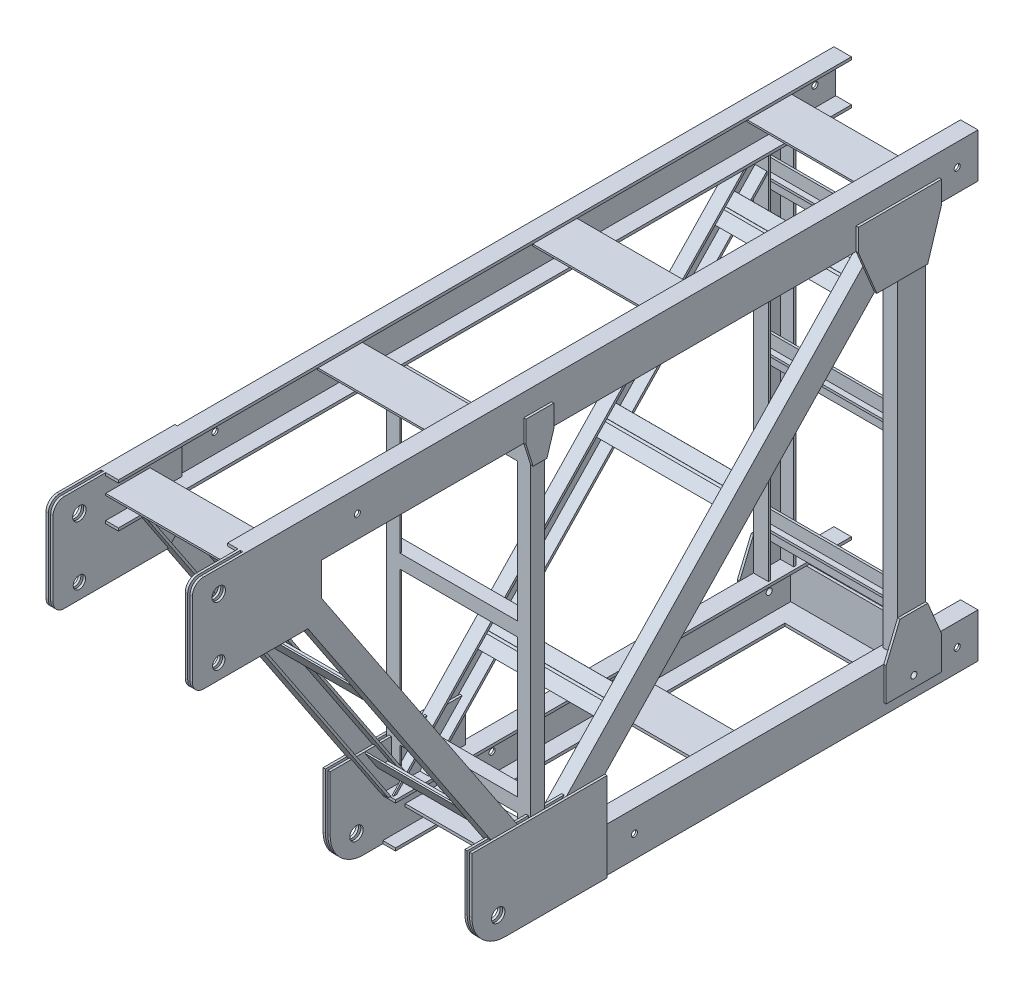
SolidWorks part; units mm, degrees
note: The reader was unsure of these and kept them because the rebuilt part matched: shared geometry of "草图38<2>".
ref_plane "前视基准面" through (0, 0, 0) normal (0, 0, 1) x (1, 0, 0)
ref_plane "上视基准面" through (0, 0, 0) normal (0, 1, 0) x (1, 0, 0)
ref_plane "右视基准面" through (0, 0, 0) normal (1, 0, 0) x (0, 0, -1)
sketch "草图2" plane through (0, 0, 0) normal (0, 0, 1) x (1, 0, 0)
  line L0 (0, 0) -> (0, 160)
  line L1 (0, 160) -> (63, 160)
  line L2 (63, 160) -> (63, 150)
  line L3 (63, 150) -> (6.5, 150)
  line L4 (6.5, 150) -> (6.5, 10)
  line L5 (6.5, 10) -> (63, 10)
  line L6 (63, 10) -> (63, 0)
  line L7 (63, 0) -> (0, 0)
  line L8 (457, 160) -> (520, 160)
  line L9 (520, 160) -> (520, 0)
  line L10 (520, 0) -> (457, 0)
  line L11 (457, 0) -> (457, 10)
  line L12 (457, 10) -> (513.5, 10)
  line L13 (513.5, 10) -> (513.5, 150)
  line L14 (513.5, 150) -> (457, 150)
  line L15 (457, 150) -> (457, 160)
  dimension "D1" = 160
  dimension "D2" = 10
  dimension "D3" = 6.5
  dimension "D4" = 63
  dimension "D5" = 520
extrude "拉伸1" add sketch "草图2" along normal blind 2835
pattern_linear "阵列(线性)2" count 2 spacing 1500 along (0, -1, 0) of "拉伸1"
sketch "草图4" plane through (0, -1340, 0) normal (0, 1, 0) x (1, 0, 0)
  line L0 (0, -2835) -> (0, 0) construction
  line L1 (520, -2835) -> (0, -2835)
  line L2 (520, -2835) -> (520, -1835)
  line L3 (520, -1835) -> (0, -1835)
  line L4 (0, -2835) -> (0, -1835)
  dimension "D1" = 1000
extrude "拉伸2" cut sketch "草图4" against normal blind 1000
sketch "草图5" plane through (0, 0, 0) normal (-1, 0, 0) x (0, 0, 1)
  line L0 (160, 95) -> (320, 95)
  line L1 (320, 95) -> (320, 88.5)
  line L2 (243.25, 88.5) -> (320, 88.5)
  line L3 (243.25, 88.5) -> (243.25, 48.5)
  line L4 (243.25, 48.5) -> (236.75, 48.5)
  line L5 (236.75, 48.5) -> (236.75, 88.5)
  line L6 (236.75, 88.5) -> (160, 88.5)
  line L7 (160, 88.5) -> (160, 95)
  line L8 (0, 160) -> (0, 0) construction
  point P10 (0, 80)
  dimension "D1" = 160
  dimension "D2" = 6.5
  dimension "D3" = 6.5
  dimension "D4" = 40
  dimension "D5" = 160
  dimension "D6" = 15
extrude "拉伸3" add sketch "草图5" against normal blind 520
sketch "草图8" plane through (0, 0, 0) normal (-1, 0, 0) x (0, 0, 1)
  line L0 (240, -1420) -> (240, 160) construction
  line L1 (2835, 160) -> (0, 160) construction
  line L2 (2835, 0) -> (0, 0) construction
  line L3 (190, 0) -> (290, 0)
  line L4 (190, 0) -> (190, -1340)
  line L5 (190, -1340) -> (290, -1340)
  line L6 (290, 0) -> (290, -1340)
  line L7 (1835, -1340) -> (0, -1340) construction
  line L9 (0, -1420) -> (1835, -1420) construction
  line L10 (0, -1340) -> (0, -1500) construction
  line L11 (1835, -1500) -> (1835, -1340) construction
  dimension "D1" = 50
  dimension "D2" = 50
  dimension "D3" = 240
extrude "拉伸7" add sketch "草图8" against normal blind 520 separate body
sketch "草图10" plane through (0, -1340, 0) normal (0, -1, 0) x (1, 0, 0)
  line L0 (466.7, 290) -> (466.7, 281.5)
  line L1 (520, 290) -> (0, 290) construction
  line L2 (466.7, 281.5) -> (514.7, 281.5)
  line L3 (514.7, 281.5) -> (514.7, 198.5)
  line L4 (514.7, 198.5) -> (466.7, 198.5)
  line L5 (466.7, 198.5) -> (466.7, 190)
  line L6 (520, 190) -> (0, 190) construction
  line L7 (53.3, 190) -> (53.3, 198.5)
  line L8 (53.3, 198.5) -> (5.3, 198.5)
  line L9 (5.3, 198.5) -> (5.3, 281.5)
  line L10 (53.3, 281.5) -> (53.3, 290)
  line L11 (53.3, 290) -> (466.7, 290)
  line L12 (5.3, 281.5) -> (53.3, 281.5)
  line L13 (53.3, 190) -> (466.7, 190)
  line L16 (0, 1835) -> (0, 0) construction
  line L17 (520, 1835) -> (520, 0) construction
  dimension "D1" = 5.3
  dimension "D2" = 5.3
  dimension "D3" = 8.5
  dimension "D4" = 48
extrude "拉伸9" cut sketch "草图10" against normal blind 1340
sketch "草图11" plane through (0, 0, 0) normal (-1, 0, 0) x (0, 0, 1)
  line L0 (2835, 160) -> (2835, 0) construction
  line L1 (2835, 80) -> (0, 80) construction
  line L2 (0, 160) -> (0, 0) construction
  circle A0 centre (2740, 80) radius 11
  dimension "D1" = 22
  dimension "D2" = 95
extrude "拉伸10" cut sketch "草图11" against normal through all
sketch "草图12" plane through (0, 0, 0) normal (-1, 0, 0) x (0, 0, 1)
  line L0 (1645, -1420) -> (290, 0) construction
  line L1 (290, 0) -> (359.1113, 0)
  line L2 (2835, 0) -> (0, 0) construction
  line L3 (359.1113, 0) -> (1637.7732, -1340)
  line L4 (1637.7732, -1340) -> (1499.5507, -1340)
  line L5 (1499.5507, -1340) -> (290, -72.4266)
  line L6 (290, -1340) -> (290, 0) construction
  line L7 (290, -72.4266) -> (290, 0)
  line L8 (0, -1420) -> (1835, -1420) construction
  line L9 (1835, -1340) -> (0, -1340) construction
  line L10 (0, -1500) -> (0, -1340) construction
  line L11 (1835, -1500) -> (1835, -1340) construction
  dimension "D1" = 50
  dimension "D2" = 50
  dimension "D3" = 190
extrude "拉伸11" add sketch "草图12" against normal blind 48
pattern_linear "阵列(线性)3" count 2 spacing 472 along (1, 0, 0) of "拉伸11"
sketch "草图13" plane through (48, 0, 0) normal (1, 0, 0) x (0, 0, -1)
  line L0 (-347.3623, 0) -> (-290, 0)
  line L1 (-359.1113, 0) -> (-290, 0) construction
  line L2 (-290, 0) -> (-290, -60.114)
  line L3 (-290, 0) -> (-290, -72.4266) construction
  line L4 (-290, -60.114) -> (-1511.2996, -1340)
  line L5 (-1499.5507, -1340) -> (-1637.7732, -1340) construction
  line L6 (-1511.2996, -1340) -> (-1626.0243, -1340)
  line L7 (-1626.0243, -1340) -> (-347.3623, 0)
  line L8 (-1637.7732, -1340) -> (-359.1113, 0) construction
  line L9 (-290, -72.4266) -> (-1499.5507, -1340) construction
  dimension "D1" = 8.5
  dimension "D2" = 8.5
extrude "拉伸12" cut sketch "草图13" against normal blind 42.7
sketch "草图14" plane through (472, 0, 0) normal (-1, 0, 0) x (0, 0, 1)
  line L0 (290, -84.7391) -> (290, 0)
  line L1 (290, 0) -> (290, -72.4266) construction
  line L2 (290, 0) -> (347.3623, 0)
  line L3 (359.1113, 0) -> (290, 0) construction
  line L4 (347.3623, 0) -> (1626.0243, -1340)
  line L5 (1499.5507, -1340) -> (1637.7732, -1340) construction
  line L6 (1626.0243, -1340) -> (1487.8018, -1340)
  line L7 (1487.8018, -1340) -> (290, -84.7391)
  line L8 (1637.7732, -1340) -> (359.1113, 0) construction
  line L9 (290, -72.4266) -> (1499.5507, -1340) construction
  dimension "D1" = 8.5
  dimension "D2" = 8.5
extrude "拉伸13" cut sketch "草图14" against normal blind 42.7
sketch "草图15" plane through (0, 0, 0) normal (-1, 0, 0) x (0, 0, 1)
  line L0 (2550, 80) -> (1550, -1420) construction
  line L1 (2496.6667, 0) -> (2448.5926, 0)
  line L2 (2835, 0) -> (359.1113, 0) construction
  line L3 (2448.5926, 0) -> (1589.197, -1289.0935)
  line L4 (1637.7732, -1340) -> (359.1113, 0) construction
  line L5 (1589.197, -1289.0935) -> (1637.7732, -1340)
  line L6 (1637.7732, -1340) -> (1651.4074, -1340)
  line L7 (1835, -1340) -> (1637.7732, -1340) construction
  line L8 (1651.4074, -1340) -> (2544.7407, 0)
  line L9 (2544.7407, 0) -> (2496.6667, 0)
  line L10 (0, -1420) -> (1835, -1420) construction
  line L11 (2740, 80) -> (0, 80) construction
  line L12 (0, 160) -> (0, 0) construction
  line L13 (1835, -1500) -> (1835, -1340) construction
  line L14 (0, -1340) -> (0, -1500) construction
  dimension "D1" = 40
  dimension "D2" = 40
  dimension "D3" = 285
  dimension "D4" = 190
extrude "拉伸14" add sketch "草图15" against normal blind 43
pattern_linear "阵列(线性)4" count 2 spacing 477 along (1, 0, 0) of "拉伸14"
sketch "草图16" plane through (477, 0, 0) normal (-1, 0, 0) x (0, 0, 1)
  line L0 (2458.2075, 0) -> (2535.1259, 0)
  line L1 (2544.7407, 0) -> (2448.5926, 0) construction
  line L2 (2535.1259, 0) -> (1641.7925, -1340)
  line L3 (1637.7732, -1340) -> (1651.4074, -1340) construction
  line L4 (1641.7925, -1340) -> (1564.8741, -1340)
  line L5 (1564.8741, -1340) -> (2458.2075, 0)
  line L6 (1651.4074, -1340) -> (2544.7407, 0) construction
  line L7 (2448.5926, 0) -> (1589.197, -1289.0935) construction
  dimension "D1" = 8
  dimension "D2" = 8
extrude "拉伸15" cut sketch "草图16" against normal blind 38
sketch "草图17" plane through (43, 0, 0) normal (1, 0, 0) x (0, 0, -1)
  line L0 (-2535.1259, 0) -> (-2458.2075, 0)
  line L1 (-2544.7407, 0) -> (-2448.5926, 0) construction
  line L2 (-2458.2075, 0) -> (-1564.8741, -1340)
  line L3 (-1637.7732, -1340) -> (-1651.4074, -1340) construction
  line L4 (-1564.8741, -1340) -> (-1641.7925, -1340)
  line L5 (-1641.7925, -1340) -> (-2535.1259, 0)
  line L6 (-1651.4074, -1340) -> (-2544.7407, 0) construction
  line L7 (-2448.5926, 0) -> (-1589.197, -1289.0935) construction
  dimension "D1" = 8
  dimension "D2" = 8
extrude "拉伸16" cut sketch "草图17" against normal blind 38
sketch "草图18" plane through (0, 0, 0) normal (-1, 0, 0) x (0, 0, 1)
  line L0 (1589.197, -1289.0935) -> (1589.197, 0.0067) construction
  line L1 (1589.197, -1289.0935) -> (359.1113, 0) construction
  line L2 (2448.5926, 0) -> (359.1113, 0) construction
  line L4 (1564.197, 0) -> (1614.197, 0)
  line L5 (1564.197, 0) -> (1564.197, -1262.8943)
  line L7 (1614.197, 0) -> (1614.197, -1251.5935)
  line L8 (2448.5926, 0) -> (1589.197, -1289.0935) construction
  line L9 (1614.197, -1251.5935) -> (1589.197, -1289.0935)
  line L10 (1589.197, -1289.0935) -> (1564.197, -1262.8943)
  dimension "D1" = 25
  dimension "D2" = 25
extrude "拉伸17" add sketch "草图18" against normal blind 520 separate body
sketch "草图19" plane through (0, 0, 0) normal (0, 1, 0) x (1, 0, 0)
  line L0 (457, -2835) -> (457, 0) construction
  line L1 (457, -1564.197) -> (63, -1564.197)
  line L2 (457, -1564.197) -> (457, -1614.197)
  line L3 (457, -1614.197) -> (63, -1614.197)
  line L4 (63, -1564.197) -> (63, -1614.197)
  line L5 (520, -1564.197) -> (0, -1564.197) construction
  line L6 (520, -1614.197) -> (0, -1614.197) construction
  line L7 (63, -2835) -> (63, 0) construction
extrude "拉伸18" cut sketch "草图19" against normal through all
sketch "草图20" plane through (457, 0, 0) normal (-1, 0, 0) x (0, 0, 1)
  line L0 (1564.197, 0) -> (1614.197, 0)
  line L1 (1614.197, 0) -> (1614.197, -1251.5935)
  line L2 (1614.197, -1251.5935) -> (1589.197, -1289.0935)
  line L3 (1589.197, -1289.0935) -> (1564.197, -1262.8943)
  line L4 (1564.197, -1262.8943) -> (1589.197, -1289.0935) construction
  line L5 (1564.197, -1262.8943) -> (1564.197, 0) construction
  line L6 (1564.197, -1262.8943) -> (1564.197, 0)
extrude "拉伸19" cut sketch "草图20" against normal blind 15
sketch "草图21" plane through (63, 0, 0) normal (1, 0, 0) x (0, 0, -1)
  line L0 (-1614.197, -1251.5935) -> (-1589.197, -1289.0935)
  line L1 (-1589.197, -1289.0935) -> (-1564.197, -1262.8943)
  line L2 (-1564.197, -1262.8943) -> (-1564.197, 0)
  line L3 (-2835, 0) -> (0, 0) construction
  line L4 (-1564.197, -1262.8943) -> (-1564.197, 0) construction
  line L5 (-1564.197, 0) -> (-1614.197, 0)
  line L6 (-1564.197, 0) -> (-1614.197, 0) construction
  line L7 (-1614.197, 0) -> (-1614.197, -1251.5935)
extrude "拉伸20" cut sketch "草图21" against normal blind 15
sketch "草图23" plane through (472, 0, 0) normal (-1, 0, 0) x (0, 0, 1)
  line L0 (1609.197, -1259.0935) -> (1589.197, -1289.0935)
  line L1 (1589.197, -1289.0935) -> (1614.197, -1251.5935) construction
  line L2 (1589.197, -1289.0935) -> (1564.197, -1262.8943)
  line L3 (1564.197, -1262.8943) -> (1564.197, 0)
  line L4 (1614.197, 0) -> (1564.197, 0) construction
  line L5 (1564.197, 0) -> (1609.197, 0)
  line L6 (1609.197, 0) -> (1609.197, -1259.0935)
  line L8 (1614.197, -1251.5935) -> (1614.197, 0) construction
  dimension "D1" = 5
extrude "拉伸21" cut sketch "草图23" against normal blind 45
sketch "草图24" plane through (48, 0, 0) normal (1, 0, 0) x (0, 0, -1)
  line L0 (-1609.197, -1259.0935) -> (-1589.197, -1289.0935)
  line L1 (-1614.197, -1251.5935) -> (-1589.197, -1289.0935) construction
  line L2 (-1589.197, -1289.0935) -> (-1564.197, -1262.8943)
  line L3 (-1564.197, -1262.8943) -> (-1564.197, 0)
  line L4 (-1564.197, 0) -> (-1609.197, 0)
  line L5 (-1564.197, 0) -> (-1614.197, 0) construction
  line L6 (-1609.197, 0) -> (-1609.197, -1259.0935)
  line L7 (-1614.197, 0) -> (-1614.197, -1251.5935) construction
  dimension "D1" = 5
extrude "拉伸22" cut sketch "草图24" against normal blind 45
pattern_linear "阵列(线性)6" count 4 spacing 775 along (0, 0, 1) of "拉伸3"
sketch "草图27" plane through (0, -1500, 0) normal (0, -1, 0) x (1, 0, 0)
  line L0 (0, 1835) -> (0, 0) construction
  line L1 (0, 240) -> (520, 240)
  line L2 (0, 240) -> (0, 80)
  line L3 (0, 80) -> (520, 80)
  line L4 (520, 240) -> (520, 80)
  line L5 (520, 1835) -> (520, 0) construction
  line L6 (0, 0) -> (63, 0) construction
  line L12 (0, 160) -> (520, 160) construction
  dimension "D1" = 160
  dimension "D2" = 80
extrude "拉伸24" add sketch "草图27" against normal blind 10
sketch "草图28" plane through (0, -1490, 0) normal (0, 1, 0) x (1, 0, 0)
  line L0 (513.5, -1835) -> (513.5, 0) construction
  line L1 (513.5, -162.5) -> (6.5, -162.5)
  line L2 (513.5, -162.5) -> (513.5, -152.5)
  line L3 (513.5, -152.5) -> (6.5, -152.5)
  line L4 (6.5, -162.5) -> (6.5, -152.5)
  line L5 (6.5, -1835) -> (6.5, 0) construction
  line L6 (63, -240) -> (63, -80) construction
  line L7 (457, -240) -> (457, -80) construction
  line L8 (63, -80) -> (457, -80) construction
  line L9 (457, -160) -> (63, -160) construction
  dimension "D1" = 10
  dimension "D2" = 5
extrude "拉伸25" add sketch "草图28" along normal blind 140
sketch "草图29" plane through (0, 0, 0) normal (-1, 0, 0) x (0, 0, 1)
  line L0 (240, -1340) -> (190, -1340) construction
  line L1 (240, -1340) -> (240, 160) construction
  line L2 (2835, 160) -> (0, 160) construction
  line L3 (231.5, -1160) -> (231.5, -1260)
  line L4 (231.5, -1260) -> (240, -1260)
  line L5 (240, -1260) -> (240, -1214.25)
  line L6 (240, -1214.25) -> (260, -1214.25)
  line L7 (260, -1214.25) -> (260, -1205.75)
  line L8 (260, -1205.75) -> (240, -1205.75)
  line L9 (240, -1205.75) -> (240, -1160)
  line L10 (240, -1160) -> (231.5, -1160)
  line L11 (190, 0) -> (190, -1340) construction
  line L12 (240, -1340) -> (290, -1340) construction
  dimension "D1" = 100
  dimension "D2" = 8.5
  dimension "D3" = 8.5
  dimension "D4" = 20
  dimension "D5" = 80
extrude "拉伸26" add sketch "草图29" against normal blind 520
pattern_linear "阵列(线性)9" count 3 spacing 550 along (0, 1, 0) of "拉伸26"
sketch "草图30" plane through (0, 0, 0) normal (-1, 0, 0) x (0, 0, 1)
  line L0 (1721.338, -1500) -> (137.3239, 160) construction
  line L1 (1835, -1500) -> (0, -1500) construction
  line L2 (2835, 160) -> (0, 160) construction
  line L3 (290, -72.4266) -> (1499.5507, -1340) construction
  line L5 (290, -72.4266) -> (326.1736, -37.9088) construction
  line L6 (326.1736, -37.9088) -> (362.3471, -3.3911) construction
  line L7 (1589.197, -1289.0935) -> (359.1113, 0) construction
  line L8 (372.0166, -98.2634) -> (441.052, -170.6106)
  line L9 (441.052, -170.6106) -> (447.2015, -164.7425)
  line L10 (447.2015, -164.7425) -> (415.6178, -131.6437)
  line L11 (415.6178, -131.6437) -> (430.0872, -117.8366)
  line L12 (430.0872, -117.8366) -> (424.2192, -111.6871)
  line L13 (424.2192, -111.6871) -> (409.7498, -125.4942)
  line L14 (409.7498, -125.4942) -> (378.1661, -92.3954)
  line L15 (378.1661, -92.3954) -> (372.0166, -98.2634)
  dimension "D1" = 100
  dimension "D2" = 8.5
  dimension "D3" = 8.5
  dimension "D4" = 20
  dimension "D5" = 80
extrude "拉伸27" add sketch "草图30" against normal blind 520
pattern_linear "阵列(线性)10" count 3 spacing 620 along (0, -0.7235, 0.6904) of "拉伸27"
sketch "草图31" plane through (520, 0, 0) normal (1, 0, 0) x (0, 0, -1)
  line L0 (-2453.9085, -59.6303) -> (-2409.5325, -126.1943)
  line L1 (-2453.9085, -59.6303) -> (-2458.0688, -62.4038)
  line L2 (-2409.5325, -126.1943) -> (-2413.6928, -128.9678)
  line L3 (-2458.0688, -62.4038) -> (-2413.6928, -128.9678)
  line L4 (-1651.4074, -1340) -> (-1618.1253, -1317.812) construction
  line L5 (-1618.1253, -1317.812) -> (-1584.8433, -1295.624) construction
  line L6 (-2603.3333, 160) -> (-1618.1253, -1317.812) construction
  line L7 (-2835, 160) -> (0, 160) construction
  line L8 (-1651.4074, -1340) -> (-2544.7407, 0) construction
  line L10 (-2448.5926, 0) -> (-1589.197, -1289.0935) construction
  line L11 (-2458.0688, -62.4038) -> (-2433.8006, -94.299) construction
  line L12 (-2453.9085, -59.6303) -> (-2413.6928, -128.9678) construction
  line L13 (-2433.8006, -94.299) -> (-2409.5325, -126.1943) construction
  dimension "D1" = 80
  dimension "D2" = 5
  dimension "D3" = 100
extrude "拉伸28" add sketch "草图31" against normal blind 520
sketch "草图32" plane through (0, -1150.9209, 1726.3814) normal (0, 0.5547, -0.8321) x (-1, 0, 0)
  line L1 (-460, 1274.0682) -> (-60, 1274.0682)
  line L2 (-460, 1274.0682) -> (-460, 1269.0682)
  line L3 (-460, 1269.0682) -> (-60, 1269.0682)
  line L4 (-60, 1274.0682) -> (-60, 1269.0682)
  line L5 (-520, 1705.7031) -> (-520, 133.128) construction
  line L6 (0, 1705.7031) -> (0, 133.128) construction
  line L7 (-260, 1231.5682) -> (-260, 1271.5682) construction
  line L8 (-5, 1231.5682) -> (-515, 1231.5682) construction
  line L9 (0, 1271.5682) -> (-520, 1271.5682) construction
  line L12 (-260, 1271.5682) -> (-260, 1311.5682) construction
  line L13 (-5, 1311.5682) -> (-515, 1311.5682) construction
  dimension "D1" = 2.5
  dimension "D2" = 2.5
  dimension "D3" = 200
  dimension "D4" = 200
extrude "拉伸29" add sketch "草图32" along normal blind 15
pattern_linear "阵列(线性)11" count 3 spacing 675 along (0, -0.8321, -0.5547) of "拉伸28", "拉伸29"
sketch "草图38" plane through (0, 0, 1614.197) normal (0, 0, 1) x (1, 0, 0)
  line L0 (0, -1251.5935) -> (0, 0) construction
  line L1 (0, -1141.5935) -> (520, -1141.5935)
  line L2 (0, -1141.5935) -> (0, -1191.5935)
  line L3 (0, -1191.5935) -> (520, -1191.5935)
  line L4 (520, -1141.5935) -> (520, -1191.5935)
  line L5 (520, -1251.5935) -> (520, 0) construction
  dimension "D1" = 50
  dimension "D2" = 60
extrude "拉伸36" add sketch "草图38" against normal blind 50
extrude "拉伸37" add sketch "草图38<2>" against normal blind 50
sketch "草图38<2>" plane through (0, 0, 1614.197) normal (0, 0, 1) x (1, 0, 0) same geometry as "草图38"
pattern_linear "阵列(线性)13" count 3 spacing 550 along (0, 1, 0) of "拉伸37"
sketch "草图39" plane through (0, 0, 1564.197) normal (0, 0, -1) x (-1, 0, 0)
  line L0 (-3, -1262.8943) -> (-3, -1191.5935) construction
  line L1 (-517, -1191.5935) -> (-3, -1191.5935)
  line L2 (-517, -1191.5935) -> (-517, -1146.5935)
  line L3 (-517, -1146.5935) -> (-3, -1146.5935)
  line L4 (-3, -1191.5935) -> (-3, -1146.5935)
  line L6 (-517, -641.5935) -> (-3, -641.5935)
  line L7 (-517, -641.5935) -> (-517, -596.5935)
  line L8 (-517, -596.5935) -> (-3, -596.5935)
  line L9 (-3, -641.5935) -> (-3, -596.5935)
  line L10 (-517, -91.5935) -> (-3, -91.5935)
  line L11 (-517, -91.5935) -> (-517, -46.5935)
  line L12 (-517, -46.5935) -> (-3, -46.5935)
  line L13 (-3, -91.5935) -> (-3, -46.5935)
  dimension "D1" = 45
extrude "拉伸38" cut sketch "草图39" against normal blind 45
sketch "草图40" plane through (520, 0, 0) normal (1, 0, 0) x (0, 0, -1)
  line L1 (-1835, -1500) -> (-1346.8747, -1500)
  line L2 (-1835, -1500) -> (-1835, -1180)
  line L3 (-1835, -1180) -> (-1346.8747, -1180)
  line L4 (-1346.8747, -1500) -> (-1346.8747, -1180)
  line L5 (-290, -72.4266) -> (-1499.5507, -1340) construction
  dimension "D1" = 320
extrude "拉伸39" add sketch "草图40" along normal blind 8.5
pattern_linear "阵列(线性)15" count 2 spacing 17 along (-1, 0, 0) of "拉伸39"
pattern_linear "阵列(线性)16" count 2 spacing 511.5 along (-1, 0, 0) of "拉伸39", "阵列(线性)15"
sketch "草图41" plane through (0, 0, 1835) normal (0, 0, 1) x (1, 0, 0)
  line L0 (63, -1500) -> (-8.5, -1500) construction
  line L1 (8.5, -1500) -> (0, -1500)
  line L2 (8.5, -1500) -> (8.5, -1340)
  line L3 (8.5, -1340) -> (0, -1340)
  line L4 (0, -1500) -> (0, -1340)
  line L5 (8.5, -1340) -> (0, -1340) construction
  line L6 (8.5, -1350) -> (8.5, -1490) construction
  line L7 (528.5, -1500) -> (457, -1500) construction
  line L8 (17, -1340) -> (503, -1340)
  line L9 (17, -1340) -> (17, -1500)
  line L10 (17, -1500) -> (503, -1500)
  line L11 (503, -1340) -> (503, -1500)
  line L12 (63, -1340) -> (17, -1340) construction
  line L13 (511.5, -1350) -> (511.5, -1490) construction
  line L14 (511.5, -1340) -> (520, -1340)
  line L15 (511.5, -1340) -> (511.5, -1500)
  line L16 (511.5, -1500) -> (520, -1500)
  line L17 (520, -1340) -> (520, -1500)
  line L18 (520, -1340) -> (511.5, -1340) construction
  line L19 (43, -1340) -> (17, -1340) construction
  line L21 (503, -1350) -> (503, -1490) construction
  dimension "D1" = 8.5
extrude "拉伸40" cut sketch "草图41" against normal blind 190
sketch "草图42" plane through (503, 0, 0) normal (-1, 0, 0) x (0, 0, 1)
  line L0 (1346.8747, -1420) -> (1335, -1420) construction
  line L1 (1404.197, -1415) -> (1564.197, -1415)
  line L2 (1404.197, -1415) -> (1404.197, -1425)
  line L3 (1404.197, -1425) -> (1564.197, -1425)
  line L4 (1564.197, -1415) -> (1564.197, -1425)
  line L5 (1346.8747, -1490) -> (1346.8747, -1350) construction
  line L8 (1564.197, 0) -> (1564.197, -1180) construction
  dimension "D1" = 10
  dimension "D2" = 160
  dimension "D3" = 5
extrude "拉伸41" add sketch "草图42" along normal blind 503
fillet "圆角1" radius 120 4 edges at (524.25, -1500, 1835) (-4.25, -1500, 1835) (12.75, -1500, 1835) (507.25, -1500, 1835)
sketch "草图43" plane through (-8.5, 0, 0) normal (-1, 0, 0) x (0, 0, 1)
  line L0 (1715, -1500) -> (1346.8747, -1500) construction
  line L1 (1835, -1180) -> (1835, -1380) construction
  circle A0 centre (1740, -1420) radius 24.25
  dimension "D1" = 48.5
  dimension "D2" = 80
  dimension "D3" = 95
extrude "拉伸42" cut sketch "草图43" against normal through all
sketch "草图44" plane through (0, 0, 0) normal (-1, 0, 0) x (0, 0, 1)
  line L1 (2835, 160) -> (2370, 160)
  line L2 (2835, 160) -> (2835, -190)
  line L3 (2835, -190) -> (2370, -190)
  line L4 (2370, 160) -> (2370, -190)
  line L5 (2448.5926, 0) -> (2515.1567, -44.376) construction
  line L6 (1758.074, -1180) -> (2544.7407, 0) construction
  line L7 (2370, -190) -> (2481.8747, -22.188) construction
  dimension "D1" = 350
extrude "拉伸43" add sketch "草图44" along normal blind 8.5
pattern_linear "阵列(线性)17" count 2 spacing 17 along (1, 0, 0) of "拉伸43"
sketch "草图45" plane through (0, 0, 2835) normal (0, 0, 1) x (1, 0, 0)
  line L0 (63, 160) -> (-8.5, 160) construction
  line L1 (0, -190) -> (8.5, -190)
  line L2 (0, -190) -> (0, 160)
  line L3 (0, 160) -> (8.5, 160)
  line L4 (8.5, -190) -> (8.5, 160)
  line L5 (8.5, -190) -> (8.5, 0) construction
  line L6 (520, 160) -> (457, 160) construction
  line L7 (17, -190) -> (513.5, -190)
  line L8 (17, -190) -> (17, 160)
  line L9 (17, 160) -> (513.5, 160)
  line L10 (513.5, -190) -> (513.5, 160)
  line L11 (513.5, 150) -> (513.5, 10) construction
extrude "拉伸44" cut sketch "草图45" against normal blind 190
chamfer "倒角1" distance 50 angle 45 2 edges at (-4.25, -190, 2370) (12.75, -190, 2370)
sketch "草图46" plane through (-8.5, 0, 0) normal (-1, 0, 0) x (0, 0, 1)
  line L0 (2835, 160) -> (2370, 160) construction
  line L2 (2835, -190) -> (2835, 160) construction
  circle A0 centre (2740, 80) radius 24.25
  dimension "D1" = 48.5
  dimension "D2" = 80
  dimension "D3" = 95
extrude "拉伸45" cut sketch "草图46" against normal through all
sketch "草图47" plane through (0, 0, 0) normal (-1, 0, 0) x (0, 0, 1)
  line L0 (140, 80) -> (140, 0)
  line L1 (190, 0) -> (0, 0) construction
  line L2 (140, 0) -> (190, -160)
  line L3 (190, -160) -> (373.5648, -160)
  line L5 (373.5648, -160) -> (440, 0)
  line L6 (1564.197, 0) -> (359.1113, 0) construction
  line L7 (440, 0) -> (440, 80)
  line L8 (440, 80) -> (140, 80)
  line L9 (190, 0) -> (190, -1340) construction
  line L10 (190, 0) -> (190, -1340) construction
  line L11 (0, 80) -> (2370, 80) construction
  line L12 (0, 160) -> (0, 0) construction
  line L13 (2370, 160) -> (2370, 0) construction
  line L14 (190, 0) -> (190, -160) construction
  line L15 (290, -72.4266) -> (1346.8747, -1180) construction
  line L17 (1346.8747, -1500) -> (0, -1500) construction
  line L21 (140, -1460) -> (340, -1460)
  line L22 (340, -1460) -> (340, -1340)
  line L24 (1346.8747, -1340) -> (290, -1340) construction
  line L26 (340, -1340) -> (290, -1220)
  line L27 (290, -1340) -> (290, -72.4266) construction
  line L29 (290, -1220) -> (190, -1220)
  line L30 (190, -1220) -> (140, -1340)
  line L31 (190, -1340) -> (0, -1340) construction
  line L32 (140, -1340) -> (140, -1460)
  line L33 (1564.197, 0) -> (1614.197, 0) construction
  line L34 (1614.197, 0) -> (1614.197, -1180) construction
  line L35 (1589.197, 0) -> (1589.197, -1180) construction
  line L36 (1564.197, -1180) -> (1614.197, -1180) construction
  line L37 (1539.197, 80) -> (1639.197, 80)
  line L38 (1639.197, 80) -> (1639.197, 0)
  line L39 (2370, 0) -> (1614.197, 0) construction
  line L40 (1639.197, 0) -> (1614.197, -80)
  line L41 (1614.197, -80) -> (1564.197, -80)
  line L42 (1564.197, 0) -> (1564.197, -1180) construction
  line L43 (1564.197, -80) -> (1539.197, 0)
  line L44 (1539.197, 0) -> (1539.197, 80)
  line L45 (1539.197, 80) -> (1589.197, 0) construction
  line L46 (1639.197, 80) -> (1589.197, 0) construction
  dimension "D1" = 300
  dimension "D2" = 50
  dimension "D3" = 120
  dimension "D4" = 200
  dimension "D5" = 40
  dimension "D6" = 100
  dimension "D7" = 80
extrude "拉伸46" add sketch "草图47" along normal blind 8.5
pattern_linear "阵列(线性)19" count 2 spacing 528.5 along (1, 0, 0) of "拉伸46"
pattern_linear "阵列(线性)20" count 2 spacing 662 along (0, 0, -1) of "拉伸41"
pattern_linear "阵列(线性)21" count 2 spacing 520 along (1, 0, 0) of "拉伸43"
pattern_linear "阵列(线性)22" count 2 spacing 503 along (1, 0, 0) of "拉伸43"
sketch "草图49" plane through (520, 0, 0) normal (1, 0, 0) x (0, 0, -1)
  line L0 (-2835, 160) -> (0, 160) construction
  line L1 (-2835, -190) -> (-2835, 160) construction
  circle A0 centre (-2740, 80) radius 24.25
  circle A1 centre (-2740, -135) radius 22.25
  dimension "D1" = 48.5
  dimension "D2" = 44.5
  dimension "D3" = 80
  dimension "D4" = 215
  dimension "D5" = 95
  dimension "D6" = 95
extrude "拉伸48" cut sketch "草图49" against normal through all
fillet "圆角2" radius 40 8 edges at (-4.25, -190, 2835) (12.75, -190, 2835) (-4.25, 160, 2835) (12.75, 160, 2835) (515.75, 160, 2835) (515.75, -190, 2835) (498.75, 160, 2835) (498.75, -190, 2835)
sketch "草图51" plane through (-8.5, 0, 0) normal (-1, 0, 0) x (0, 0, 1)
  line L0 (1740, -1420) -> (0, -1420) construction
  line L1 (2740, 80) -> (0, 80) construction
  line L2 (0, 160) -> (0, 0) construction
  line L3 (0, -1340) -> (0, -1500) construction
  circle A0 centre (2240, 80) radius 11
  circle A1 centre (1240, -1420) radius 11
  circle A2 centre (240, -1420) radius 11
  circle A3 centre (75, 80) radius 11
  circle A4 centre (75, -1420) radius 11
  dimension "D1" = 75
  dimension "D2" = 22
  dimension "D3" = 500
  dimension "D4" = 500
  dimension "D5" = 1000
  dimension "D6" = 75
extrude "拉伸50" cut sketch "草图51" against normal through all
